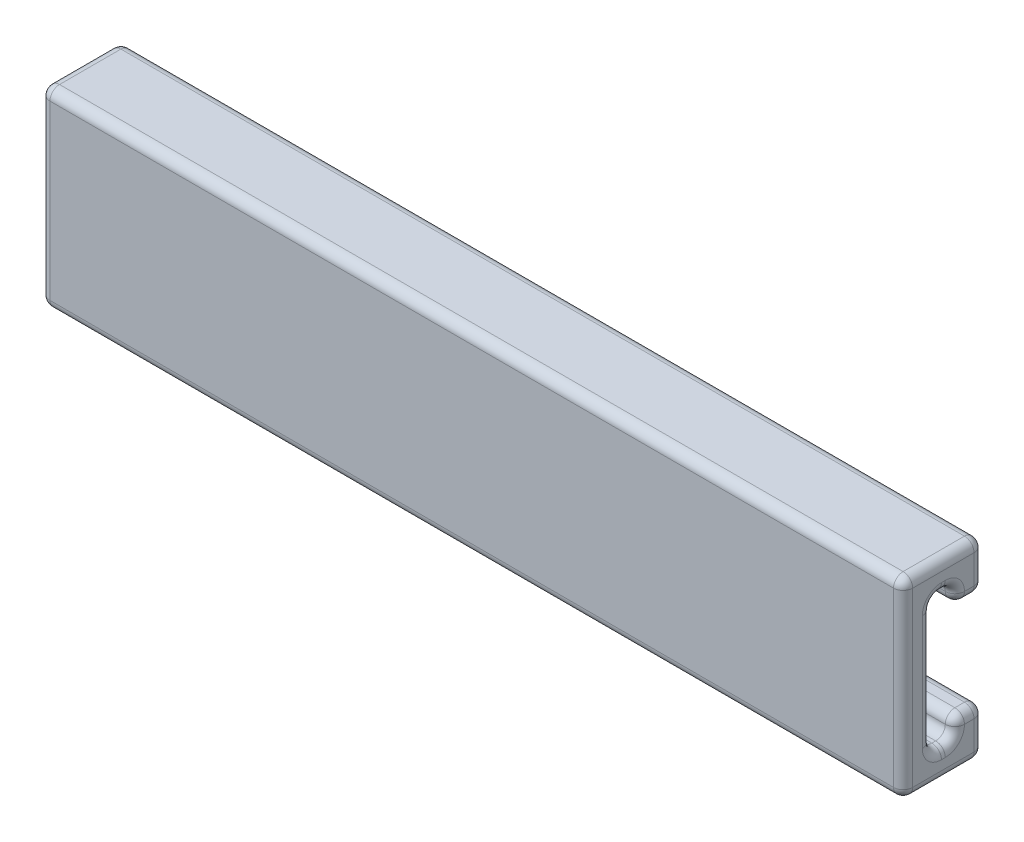
SolidWorks part; units mm, degrees
ref_plane "Front Plane" through (0, 0, 0) normal (0, 0, 1) x (1, 0, 0)
ref_plane "Top Plane" through (0, 0, 0) normal (0, 1, 0) x (1, 0, 0)
ref_plane "Right Plane" through (0, 0, 0) normal (1, 0, 0) x (0, 0, -1)
sketch "Sketch1" plane through (0, 0, 0) normal (1, 0, 0) x (0, 0, -1)
  line L0 (0, 8.89) -> (0, -8.89)
  line L1 (0, -8.89) -> (3.048, -8.89)
  line L2 (3.048, -8.89) -> (3.048, -6.35)
  line L3 (3.048, -6.35) -> (6.858, -6.35)
  line L4 (6.858, -6.35) -> (6.858, -12.7)
  line L5 (6.858, -12.7) -> (-3.81, -12.7)
  line L6 (-3.81, -12.7) -> (-3.81, 12.7)
  line L7 (-3.81, 12.7) -> (6.858, 12.7)
  line L8 (6.858, 12.7) -> (6.858, 6.35)
  line L9 (6.858, 6.35) -> (3.048, 6.35)
  line L10 (3.048, 6.35) -> (3.048, 8.89)
  line L11 (3.048, 8.89) -> (0, 8.89)
  line L12 (3.048, 8.89) -> (6.858, 8.89) construction
  line L13 (3.048, 8.89) -> (3.048, 12.7) construction
  line L14 (0, 8.89) -> (-3.81, 8.89) construction
  dimension "D1" = 3.048
  dimension "D2" = 3.81
  dimension "D3" = 17.78
  dimension "D4" = 2.54
extrude "Boss-Extrude1" add sketch "Sketch1" along normal blind 114.3
fillet "Fillet1" radius 1.27 4 edges at (57.15, 8.89, -3.048) (57.15, 8.89, 0) (57.15, -8.89, -3.048) (57.15, -8.89, 0)
fillet "Fillet2" radius 1.27 36 edges at (57.15, 6.35, -3.048) (57.15, -6.35, -6.858) (57.15, 6.35, -6.858) (57.15, -6.35, -3.048) (0, 8.518, -2.676) (0, 6.35, -4.953) (0, 9.525, -6.858) (0, -9.525, -6.858) (0, -6.35, -4.953) (0, -8.518, -2.676) (0, -8.89, -1.524) (0, -8.518, -0.372) (0, 0, 0) (0, 8.518, -0.372) (0, 8.89, -1.524) (57.15, -12.7, -6.858) (0, -12.7, -1.524) (57.15, -12.7, 3.81) (0, 0, 3.81) (114.3, -8.518, -0.372) (114.3, -8.89, -1.524) (114.3, -8.518, -2.676) (114.3, -6.35, -4.953) (114.3, -9.525, -6.858) (114.3, -12.7, -1.524) (114.3, 0, 3.81) (114.3, 9.525, -6.858) (114.3, 6.35, -4.953) (114.3, 8.518, -2.676) (114.3, 8.89, -1.524) (114.3, 8.518, -0.372) (114.3, 0, 0) (57.15, 12.7, -6.858) (114.3, 12.7, -1.524) (57.15, 12.7, 3.81) (0, 12.7, -1.524)
